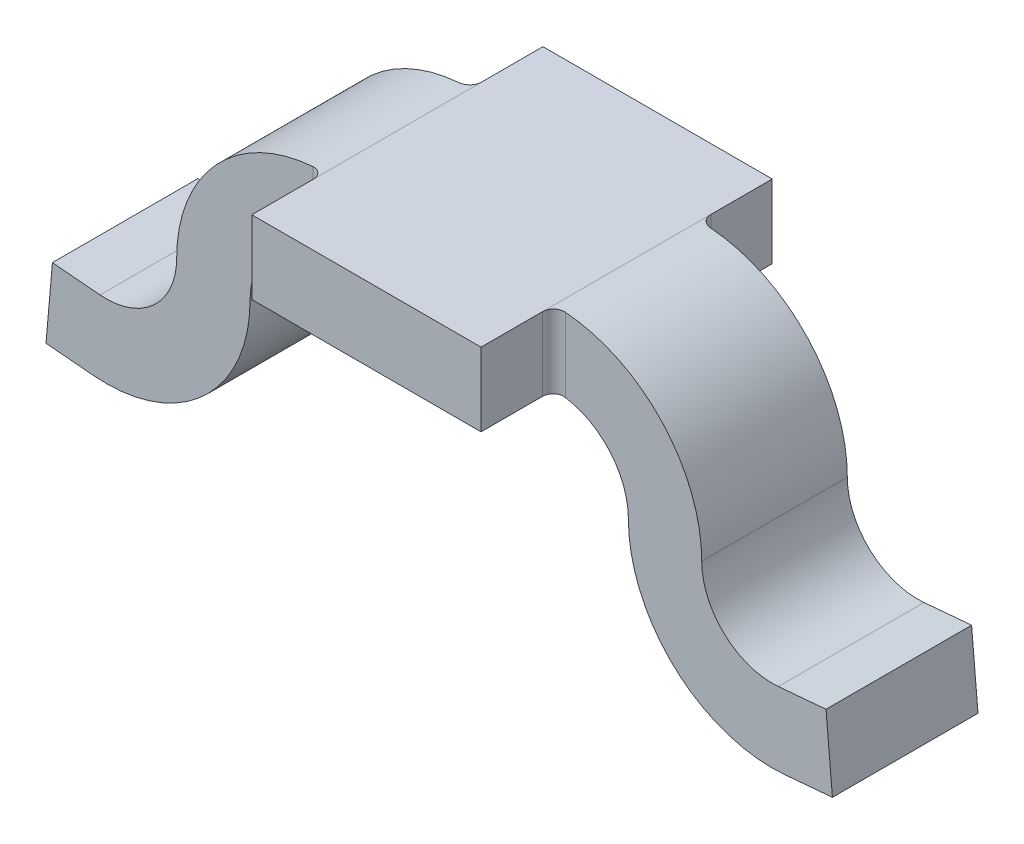
SolidWorks part; units mm, degrees
ref_plane "Front Plane" through (0, 0, 0) normal (0, 0, 1) x (1, 0, 0)
ref_plane "Top Plane" through (0, 0, 0) normal (0, 1, 0) x (1, 0, 0)
ref_plane "Right Plane" through (0, 0, 0) normal (1, 0, 0) x (0, 0, -1)
sketch "Sketch1" plane through (0, 0, 0) normal (0, 0, 1) x (1, 0, 0)
  line L0 (1, 0) -> (-1, 0)
  line L1 (0, 0) -> (0, -2.8749) construction
  line L2 (-3.0141, -1.9) -> (-3.43, -1.8636)
  line L3 (3.0141, -1.9) -> (3.43, -1.8636)
  line L4 (-2.9584, -1.2624) -> (-3.3742, -1.2261)
  line L5 (1, 0.64) -> (-1, 0.64)
  line L6 (2.9584, -1.2624) -> (3.3742, -1.2261)
  line L7 (-3.3742, -1.2261) -> (-3.43, -1.8636)
  line L8 (3.3742, -1.2261) -> (3.43, -1.8636)
  arc A0 (-1, 0) -> (-1.65, -0.65) centre (-1, -0.65) ccw
  arc A1 (-1.65, -0.65) -> (-3.0141, -1.9) centre (-2.9048, -0.65) cw
  arc A2 (1.65, -0.65) -> (3.0141, -1.9) centre (2.9048, -0.65) ccw
  arc A3 (1, 0) -> (1.65, -0.65) centre (1, -0.65) cw
  arc A4 (-2.29, -0.65) -> (-2.9584, -1.2624) centre (-2.9048, -0.65) cw
  arc A5 (-1, 0.64) -> (-2.29, -0.65) centre (-1, -0.65) ccw
  arc A6 (1, 0.64) -> (2.29, -0.65) centre (1, -0.65) cw
  arc A7 (2.29, -0.65) -> (2.9584, -1.2624) centre (2.9048, -0.65) ccw
  dimension "D1" = 3.3
  dimension "D2" = 2
  dimension "D3" = 5
  dimension "D4" = 1.78
  dimension "D5" = 1.9
  dimension "D6" = 0.64
extrude "Boss-Extrude1" add sketch "Sketch1" along normal mid plane 3
sketch "Sketch2" plane through (0, 0, 0) normal (0, 1, 0) x (1, 0, 0)
  line L0 (-3.43, -1.5) -> (-3.43, 1.5) construction
  line L1 (3.43, -1.5) -> (3.43, 1.5) construction
  line L2 (-1, 1.27) -> (1, 1.27)
  line L4 (1, -1.5) -> (1, 1.5) construction
  line L5 (1, 1.27) -> (1, 0.635)
  line L6 (1, 0.635) -> (3.43, 0.635)
  line L7 (3.43, 0.635) -> (3.43, -0.635)
  line L8 (0, 0) -> (0, 1.27) construction
  line L9 (0, 0) -> (3.43, 0) construction
  line L10 (-3.43, 0.635) -> (-3.43, -0.635)
  line L11 (-1, 0.635) -> (-3.43, 0.635)
  line L12 (-1, 1.27) -> (-1, 0.635)
  line L13 (-1, -0.635) -> (-3.43, -0.635)
  line L14 (-1, -1.27) -> (-1, -0.635)
  line L15 (-1, -1.27) -> (1, -1.27)
  line L16 (1, -1.27) -> (1, -0.635)
  line L17 (1, -0.635) -> (3.43, -0.635)
  point P18 (-3.43, 0)
  dimension "D1" = 6.86
  dimension "D2" = 1.27
  dimension "D3" = 2.54
extrude "Cut-Extrude1" cut sketch "Sketch2" against normal through all both and the other way through all flip side to cut
fillet "Fillet1" radius 0.1 4 edges at (-1, 0.32, -0.635) (1, 0.32, -0.635) (1, 0.32, 0.635) (-1, 0.32, 0.635)
